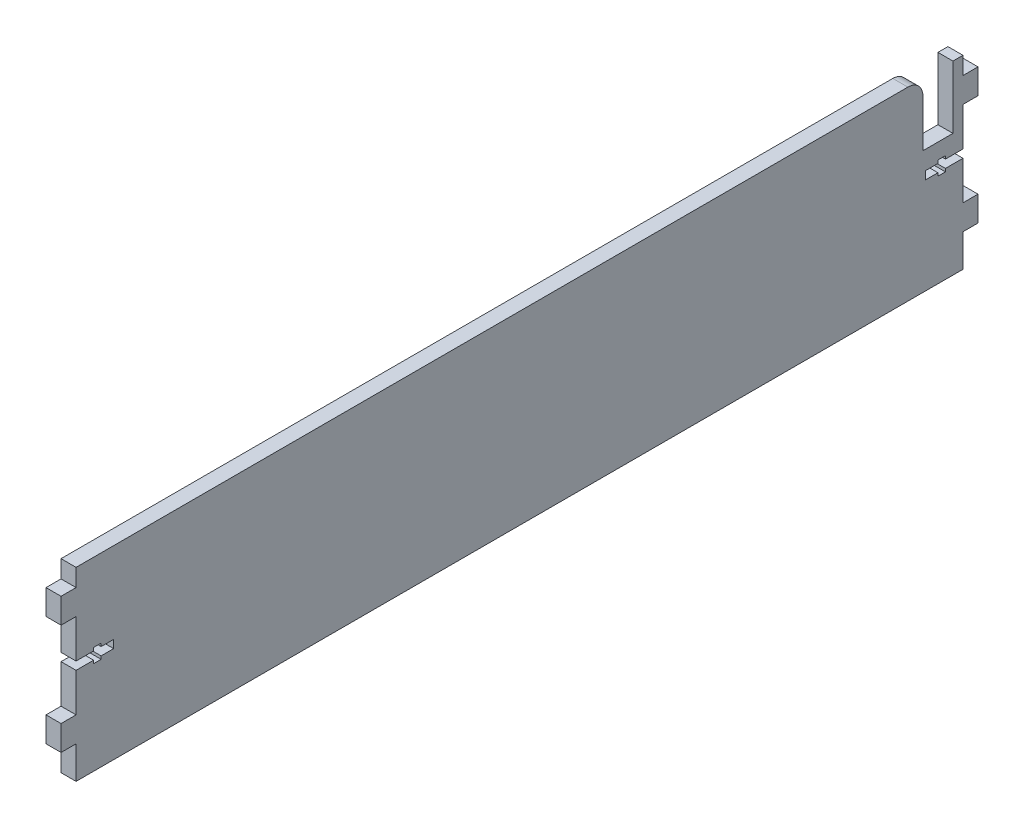
SolidWorks part; units mm, degrees
ref_plane "Front Plane" through (0, 0, 0) normal (0, 0, 1) x (1, 0, 0)
ref_plane "Top Plane" through (0, 0, 0) normal (0, 1, 0) x (1, 0, 0)
ref_plane "Right Plane" through (0, 0, 0) normal (1, 0, 0) x (0, 0, -1)
sketch "Sketch1" plane through (0, 0, 0) normal (1, 0, 0) x (0, 0, -1)
  line L1 (-177, -40) -> (177, -40)
  line L2 (-177, -40) -> (-177, 40)
  line L3 (-177, 40) -> (177, 40)
  line L4 (177, -40) -> (177, 40)
  line L5 (-177, -40) -> (177, 40) construction
  line L6 (-177, 40) -> (177, -40) construction
  point P0 (0, 0)
  dimension "D1" = 80
  dimension "D2" = 354
extrude "Boss-Extrude1" add sketch "Sketch1" along normal blind 6
sketch "Sketch4" plane through (0, 0, 177) normal (0, 0, 1) x (1, 0, 0)
  line L1 (6, 27) -> (0, 27) construction
  line L2 (6, 17) -> (6, 27) construction
  line L3 (0, 27) -> (0, 17) construction
  line L4 (0, 17) -> (6, 17) construction
  line L7 (6, -17) -> (0, -17) construction
  line L8 (6, -27) -> (6, -17) construction
  line L9 (0, -17) -> (0, -27) construction
  line L10 (0, -27) -> (6, -27) construction
  line L13 (6, 27) -> (0, 27)
  line L14 (6, 17) -> (6, 27)
  line L15 (0, 27) -> (0, 17)
  line L16 (0, 17) -> (6, 17)
  line L17 (6, -17) -> (0, -17)
  line L18 (6, -27) -> (6, -17)
  line L19 (0, -17) -> (0, -27)
  line L20 (0, -27) -> (6, -27)
extrude "Boss-Extrude2" add sketch "Sketch4" along normal blind 6
sketch "Sketch5" plane through (0, 0, 0) normal (-1, 0, 0) x (0, 0, 1)
  line L0 (177, 17) -> (177, -17) construction
  line L7 (0, 0) -> (0, -20.5925) construction
  line L8 (-177, 1.6) -> (-170, 1.6)
  line L9 (-167, 2.8) -> (-170, 2.8)
  line L10 (-167, 1.6) -> (-162, 1.6)
  line L11 (-162, -1.6) -> (-162, 1.6)
  line L12 (-167, -1.6) -> (-162, -1.6)
  line L13 (-167, -2.8) -> (-170, -2.8)
  line L14 (-177, -1.6) -> (-170, -1.6)
  line L15 (-170, -2.8) -> (-170, -1.6)
  line L16 (-170, 1.6) -> (-170, 2.8)
  line L17 (-167, 1.6) -> (-167, 2.8)
  line L18 (-167, -2.8) -> (-167, -1.6)
  line L19 (183, -1.6) -> (183, 1.6) construction
  line L20 (183, -1.6) -> (183, 1.6)
  line L21 (183, 0) -> (146.4296, 0) construction
  line L25 (177, -1.6) -> (177, 1.6)
  line L26 (167, -2.8) -> (167, -1.6)
  line L27 (167, 1.6) -> (167, 2.8)
  line L28 (170, 1.6) -> (170, 2.8)
  line L29 (170, -2.8) -> (170, -1.6)
  line L30 (177, -1.6) -> (170, -1.6)
  line L31 (167, -2.8) -> (170, -2.8)
  line L32 (167, -1.6) -> (162, -1.6)
  line L33 (162, -1.6) -> (162, 1.6)
  line L34 (167, 1.6) -> (162, 1.6)
  line L35 (167, 2.8) -> (170, 2.8)
  line L36 (177, 1.6) -> (170, 1.6)
  line L37 (-177, -1.6) -> (-177, 1.6)
  line L38 (-183, -1.6) -> (-183, 1.6)
  point P0 (177, 0)
  dimension "D1" = 15
  dimension "D2" = 5.6
  dimension "D3" = 3.2
  dimension "D4" = 7
  dimension "D5" = 3
extrude "Cut-Extrude3" cut sketch "Sketch5" against normal up to next contours L25 L36 L28 L35 L27 L34 L33 L32 L26 L31 L29 L30 | L37 L14 L15 L13 L18 L12 L11 L10 L17 L9 L16 L8 region at (0, 0, -169.3696) region at (0, 0, 169.3696)
sketch "Sketch7" plane through (0, 0, -177) normal (0, 0, -1) x (-1, 0, 0)
  line L1 (-6, 27) -> (0, 27)
  line L2 (-6, 27) -> (-6, 17)
  line L3 (-6, 17) -> (0, 17)
  line L4 (0, 27) -> (0, 17)
  line L6 (-6, -17) -> (0, -17)
  line L7 (-6, -17) -> (-6, -27)
  line L8 (-6, -27) -> (0, -27)
  line L9 (0, -17) -> (0, -27)
  line L11 (0, 1.6) -> (0, 40) construction
  line L12 (0, 17) -> (-6, 17) construction
  line L13 (-6, 1.6) -> (-6, 40) construction
  line L14 (-6, 27) -> (0, 27) construction
  line L15 (-6, -40) -> (-6, -1.6) construction
  line L16 (0, -40) -> (0, -1.6) construction
  line L17 (-6, -17) -> (0, -17) construction
  line L18 (0, -27) -> (-6, -27) construction
extrude "Boss-Extrude3" add sketch "Sketch7" along normal blind 6
sketch "Sketch8" plane through (0, 40, 0) normal (0, 1, 0) x (1, 0, 0)
  line L1 (0, 177) -> (6, 177)
  line L2 (0, 177) -> (0, -177)
  line L3 (0, -177) -> (6, -177)
  line L4 (6, 177) -> (6, -177)
extrude "Cut-Extrude4" cut sketch "Sketch8" against normal blind 6
sketch "Sketch9" plane through (0, 34, 0) normal (0, 1, 0) x (1, 0, 0)
  line L0 (0, 177) -> (0, -177) construction
  line L1 (0, 173) -> (6, 173)
  line L2 (0, 173) -> (0, 161)
  line L3 (0, 161) -> (6, 161)
  line L4 (6, 173) -> (6, 161)
  line L5 (6, -177) -> (6, 177) construction
  line L6 (325.5, 177) -> (-102.5, 177) construction
  dimension "D1" = 4
  dimension "D2" = 12
extrude "Cut-Extrude5" cut sketch "Sketch9" against normal blind 25
fillet "Fillet1" radius 6 1 edges at (3, 34, -161)
